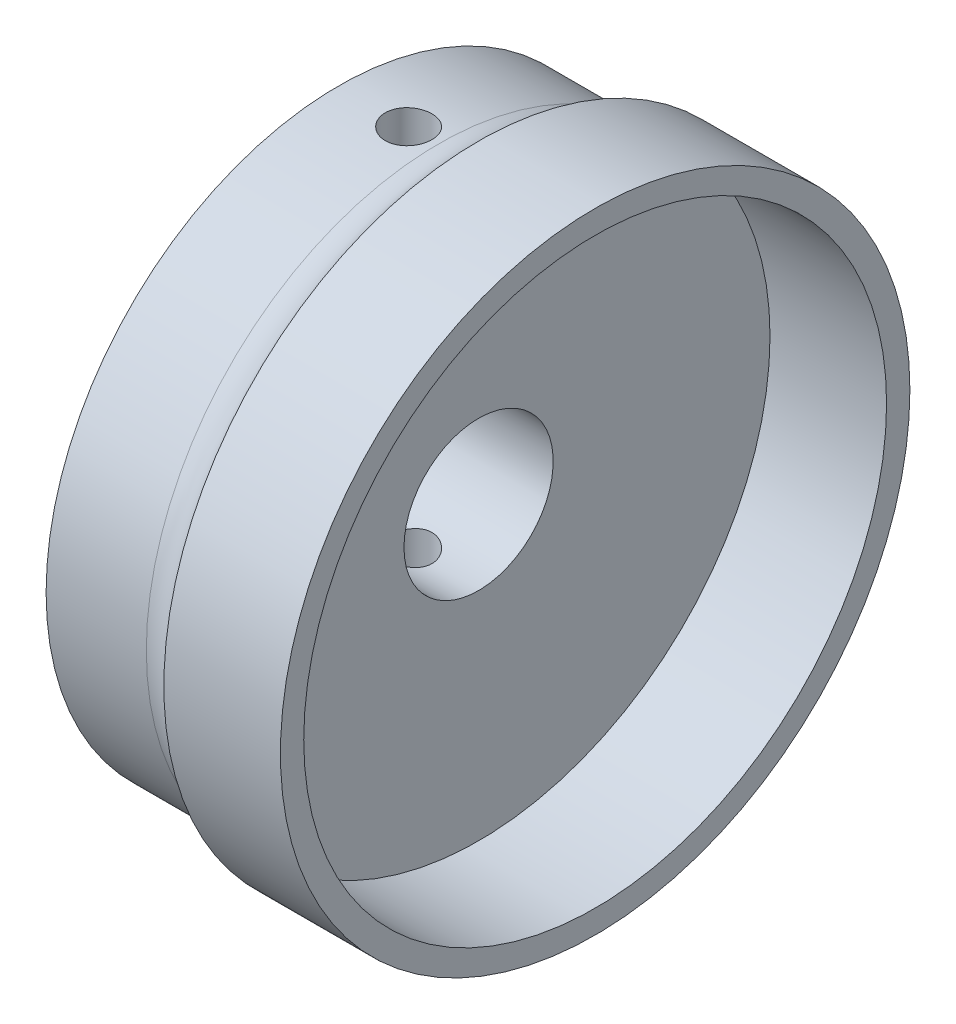
SolidWorks part; units mm, degrees
ref_plane "前视基准面" through (0, 0, 0) normal (0, 0, 1) x (1, 0, 0)
ref_plane "上视基准面" through (0, 0, 0) normal (0, 1, 0) x (1, 0, 0)
ref_plane "右视基准面" through (0, 0, 0) normal (1, 0, 0) x (0, 0, -1)
other "Configuration Table"
sketch "草图1" plane through (0, 0, 0) normal (1, 0, 0) x (0, 0, -1)
  circle A0 centre (0, 0) radius 12.55
  dimension "D1" = 25.1
extrude "凸台-拉伸1" add sketch "草图1" along normal blind 6
sketch "草图2" plane through (0, 0, 0) normal (-1, 0, 0) x (0, 0, 1)
  circle A0 centre (0, 0) radius 3.2
  dimension "D1" = 6.4
extrude "切除-拉伸1" cut sketch "草图2" against normal blind 6
sketch "草图3" plane through (0, 0, 0) normal (0, 1, 0) x (1, 0, 0)
  line L0 (0, 12.55) -> (0, -12.55) construction
  circle A0 centre (3, 0) radius 1
  dimension "D1" = 2
  dimension "D2" = 3
extrude "切除-拉伸2" cut sketch "草图3" against normal up to next and the other way up to next
sketch "草图4" plane through (6, 0, 0) normal (1, 0, 0) x (0, 0, -1)
  circle A0 centre (0, 0) radius 13.5
  dimension "D1" = 27
extrude "凸台-拉伸2" add sketch "草图4" along normal blind 5
sketch "草图5" plane through (11, 0, 0) normal (1, 0, 0) x (0, 0, -1)
  circle A0 centre (0, 0) radius 12.5
  dimension "D1" = 25
extrude "切除-拉伸3" cut sketch "草图5" against normal blind 5
fillet "圆角2" radius 2 1 edges at (6, 0, -12.55)
